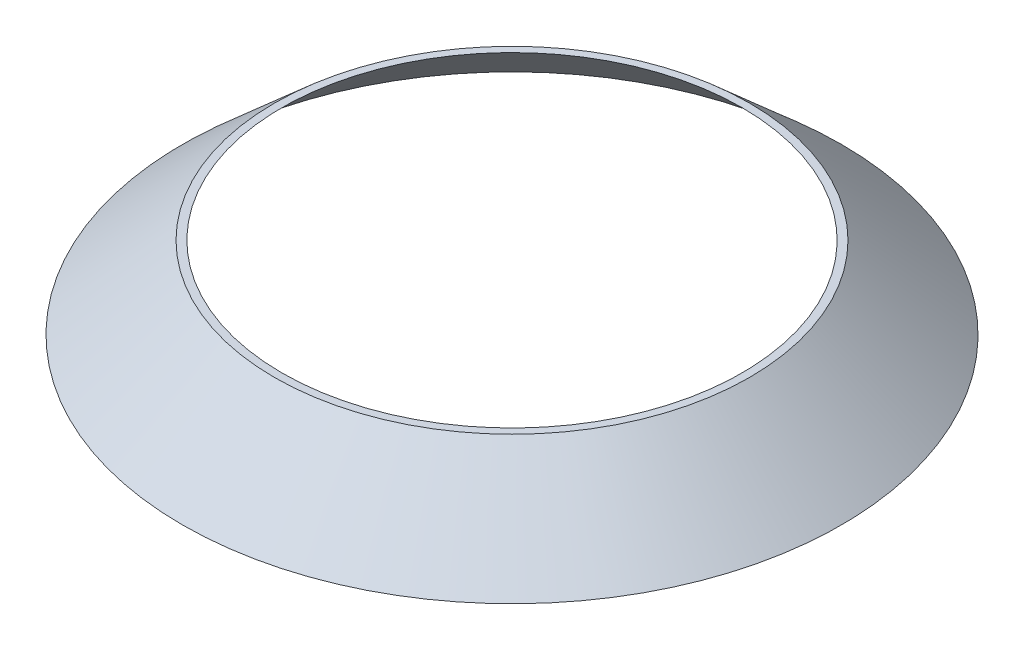
SolidWorks part; units mm, degrees
ref_plane "Front Plane" through (0, 0, 0) normal (0, 0, 1) x (1, 0, 0)
ref_plane "Top Plane" through (0, 0, 0) normal (0, 1, 0) x (1, 0, 0)
ref_plane "Right Plane" through (0, 0, 0) normal (1, 0, 0) x (0, 0, -1)
sketch "Sketch1" plane through (0, 0, 0) normal (0, 1, 0) x (1, 0, 0)
  circle A0 centre (0, 0) radius 31.5
  circle A1 centre (0, 0) radius 32.25
  dimension "D1" = 64.5
  dimension "D2" = 63
ref_plane "Plane1" through (0, 8, 0) normal (0, 1, 0) x (1, 0, 0)
sketch "Sketch2" plane through (0, 8, 0) normal (0, 1, 0) x (1, 0, 0)
  circle A0 centre (0, 0) radius 23.25
  circle A1 centre (0, 0) radius 22.5
  dimension "D1" = 46.5
  dimension "D2" = 45
loft "Loft2" add section "Sketch1" section "Sketch2" connector at (-23.7848, 0, 21.7795) connector at (-17.1934, 8, 15.6509)
loft "Cut-Loft1" cut section "Sketch2<5>" section "Sketch1<52>" connector at (-18.2736, 8, 13.1273) connector at (-25.2966, 0, 18.7705)
sketch "Sketch2<5>" plane through (0, 8, 0) normal (0, 1, 0) x (1, 0, 0) same geometry as "Sketch2"
sketch "Sketch1<52>" plane through (0, 0, 0) normal (0, 1, 0) x (1, 0, 0) same geometry as "Sketch1"
